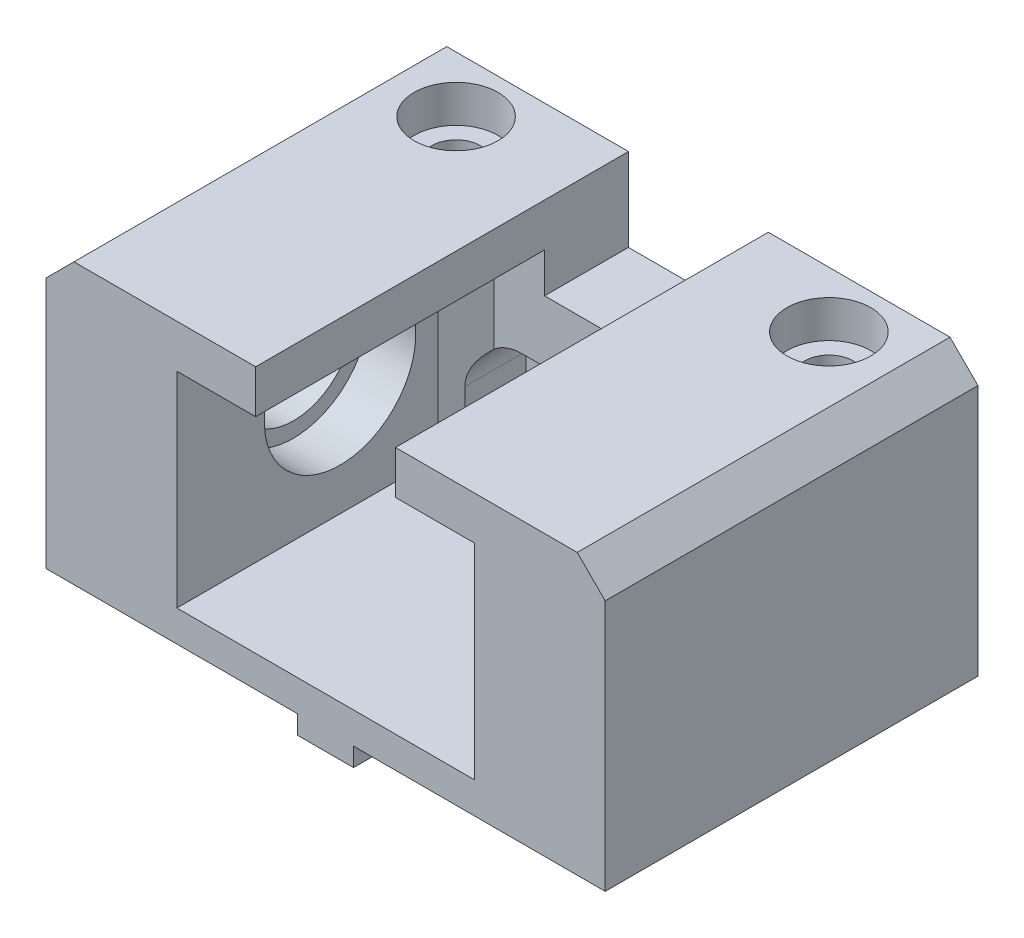
SolidWorks part; units mm, degrees
ref_plane "Front Plane" through (0, 0, 0) normal (0, 0, 1) x (1, 0, 0)
ref_plane "Top Plane" through (0, 0, 0) normal (0, 1, 0) x (1, 0, 0)
ref_plane "Right Plane" through (0, 0, 0) normal (1, 0, 0) x (0, 0, -1)
sketch "Sketch1" plane through (0, 0, 0) normal (0, 0, 1) x (1, 0, 0)
  line L0 (-7.5041, -0.2533) -> (-7.5041, -0.2824)
  line L1 (-5.65, -17.9827) -> (-5.65, -12.3454)
  line L2 (-5.65, -12.3454) -> (-5.15, -11.8454)
  line L3 (5.15, -11.8454) -> (5.65, -12.3454)
  line L4 (0, -17.9827) -> (0, 9.9476) construction
  line L5 (5.65, -17.9827) -> (5.65, -12.3454)
  line L6 (30, -21.3412) -> (30, 8.6588)
  line L7 (-15.9522, -17.9827) -> (15.9522, -17.9827)
  line L8 (-5.15, -11.8454) -> (5.15, -11.8454)
  line L27 (-30, -21.3412) -> (30, -21.3412)
  line L28 (-30, 8.6588) -> (-7.5, 8.6588)
  line L29 (7.5, 8.6588) -> (30, 8.6588)
  line L31 (15.9522, -17.9827) -> (15.9522, 4.0173)
  line L32 (-30, -21.3412) -> (-30, 8.6588)
  line L33 (-15.9522, 4.0173) -> (-7.5021, 4.0173)
  line L34 (7.5021, 4.0173) -> (15.9522, 4.0173)
  line L35 (-7.5, 8.6588) -> (-7.5021, 4.0173)
  line L36 (7.5, 8.6588) -> (7.5021, 4.0173)
  line L38 (-15.9522, -17.9827) -> (-15.9522, 4.0173)
  circle A2 centre (-10, -11.3412) radius 2.6
  circle A3 centre (10, -11.3412) radius 2.6
  point P3 (-5.65, -11.8454)
  point P7 (5.65, -11.8454)
  point P8 (-5.65, -11.3454)
  point P11 (5.65, -11.3454)
  dimension "D6" = 7.5
  dimension "D2" = 15
  dimension "D3" = 0.5
  dimension "D12" = 0.5
  dimension "D4" = 60
  dimension "D5" = 30
  dimension "D7" = 10
  dimension "D8" = 10
  dimension "D9" = 22
extrude "Boss-Extrude1" add sketch "Sketch1" along normal blind 40
sketch "Sketch2" plane through (0, 0, 0) normal (0, 0, -1) x (-1, 0, 0)
  line L0 (-7.5021, 4.0173) -> (-15.9522, 4.0173) construction
  line L1 (-15.9522, -17.9827) -> (-15.9522, 4.0173) construction
  line L3 (15.9522, -17.9827) -> (15.9522, 4.0173) construction
  line L4 (15.9522, 4.0173) -> (7.5021, 4.0173) construction
  line L5 (7.5, 8.6588) -> (7.5021, 4.0173) construction
  line L12 (5.5, -18.3454) -> (5.5244, -12.4844) construction
  line L13 (6.9689, -13.3454) -> (-4.795, -13.3457) construction
  line L14 (-7.5021, 8.6585) -> (-7.5021, -0.2536)
  line L15 (5.0208, -13.3455) -> (-5, -13.3457)
  line L16 (5.5188, -13.8455) -> (5.0208, -13.3455)
  line L17 (7.5041, -0.2533) -> (7.5041, -0.2824) construction
  line L19 (-7.5021, 4.0173) -> (-15.9522, 4.0173)
  line L20 (-15.9522, -17.9827) -> (-15.9522, 4.0173)
  line L22 (15.9522, -17.9827) -> (15.9522, 4.0173)
  line L23 (15.9522, 4.0173) -> (7.5021, 4.0173)
  line L24 (7.5, 8.6588) -> (7.5041, -0.2533)
  line L27 (30, -21.3454) -> (-28, -21.3454)
  line L31 (-5.5, -18.3457) -> (-5.5, -13.3436) construction
  line L32 (-5, -13.3457) -> (-5.5, -13.8457)
  line L33 (0, -18.3454) -> (0, -21.3454) construction
  line L36 (7.5041, -0.2533) -> (7.5041, -0.2824)
  line L37 (7.5041, -0.2533) -> (-7.5021, -0.2536)
  line L38 (5.5, -18.3454) -> (5.5188, -13.8455)
  line L42 (-5.5, -18.3457) -> (-5.5, -13.8457)
  line L54 (5.0298, -11.1846) -> (6.9689, -13.3454) construction
  line L55 (5, -18.3433) -> (5.0298, -11.1846) construction
  line L56 (5.8484, -12.8454) -> (-5.0021, -12.8457) construction
  line L57 (5.5244, -12.4844) -> (5.8484, -12.8454) construction
  line L58 (-5.0021, -12.8457) -> (-5.5, -13.3436) construction
  line L59 (-5, -18.3457) -> (-5, -13.5507) construction
  line L60 (-4.795, -13.3457) -> (-5, -13.5507) construction
  circle A0 centre (-10, -11.3412) radius 2.6 construction
  circle A1 centre (10, -11.3412) radius 2.6 construction
  circle A2 centre (-10, -11.3412) radius 2.6
  circle A3 centre (10, -11.3412) radius 2.6
  point P18 (5.5208, -13.3455)
  point P21 (-5.5, -13.3457)
  point P35 (5.65, -11.3454)
  point P38 (-5.15, -11.3454)
  point P40 (-5.65, -11.3454)
  point P42 (5.65, -11.3454)
  point P43 (-5.65, -11.3454)
  dimension "D2" = 5
  dimension "D3" = 11
  dimension "D1" = 0.5
  dimension "D11" = 0.5
  dimension "D4" = 5.5
extrude "Boss-Extrude2" add sketch "Sketch2" against normal blind 9
sketch "Sketch3" plane through (0, 0, 9) normal (0, 0, 1) x (1, 0, 0)
  circle A0 centre (-10, -11.3412) radius 4.5
  circle A1 centre (10, -11.3412) radius 4.5
  dimension "D1" = 9
extrude "Cut-Extrude1" cut sketch "Sketch3" against normal blind 5
sketch "Sketch4" plane through (0, 8.6588, 0) normal (0, 1, 0) x (1, 0, 0)
  line L0 (0, 0) -> (0, -35) construction
  circle A0 centre (-20, -6) radius 2.6
  circle A1 centre (20, -6) radius 2.6
  dimension "D1" = 5.2
  dimension "D2" = 6
  dimension "D3" = 20
extrude "Cut-Extrude2" cut sketch "Sketch4" against normal through all
chamfer "Chamfer1" distance 3 angle 45 2 edges at (-15.9522, -6.9827, 9) (15.9522, -6.9827, 9)
sketch "Sketch5" plane through (-30, 0, 0) normal (-1, 0, 0) x (0, 0, 1)
  circle A0 centre (22.5, -5.3412) radius 6.5
  dimension "D1" = 13
  dimension "D2" = 17.5
  dimension "D3" = 16
extrude "Cut-Extrude3" cut sketch "Sketch5" against normal blind 55
sketch "Sketch6" plane through (-30, 0, 0) normal (-1, 0, 0) x (0, 0, 1)
  circle A0 centre (22.5, -5.3412) radius 8.125
  dimension "D1" = 16.25
extrude "Cut-Extrude4" cut sketch "Sketch6" against normal blind 5
sketch "Sketch7" plane through (-15.9522, 0, 0) normal (1, 0, 0) x (0, 0, -1)
  circle A0 centre (-22.5, -5.3412) radius 8.125
  dimension "D1" = 16.25
extrude "Cut-Extrude5" cut sketch "Sketch7" against normal blind 5
sketch "Sketch8" plane through (15.9522, 0, 0) normal (-1, 0, 0) x (0, 0, 1)
  circle A0 centre (22.5, -5.3412) radius 8.125
  dimension "D1" = 16.25
extrude "Cut-Extrude6" cut sketch "Sketch8" against normal blind 5
sketch "Sketch9" plane through (0, 8.6588, 0) normal (0, 1, 0) x (1, 0, 0)
  circle A0 centre (20, -6) radius 4.5
  circle A1 centre (-20, -6) radius 4.5
  dimension "D1" = 9
extrude "Cut-Extrude7" cut sketch "Sketch9" against normal blind 4
chamfer "Chamfer2" distance 3 angle 45 2 edges at (-30, 8.6588, 20) (30, 8.6588, 20)
sketch "Sketch10" plane through (0, -21.3412, 0) normal (0, -1, 0) x (1, 0, 0)
  line L0 (0, 40) -> (0, 0) construction
  line L1 (-30, 40) -> (30, 40) construction
  line L2 (-30, 0) -> (30, 0) construction
  line L3 (-3, 40) -> (-3, 0)
  line L4 (3, 40) -> (3, 0)
  line L5 (3, 40) -> (-3, 40)
  line L6 (3, 0) -> (-3, 0)
  dimension "D1" = 3
extrude "Boss-Extrude3" add sketch "Sketch10" along normal blind 2
sketch "Sketch11" plane through (0, 0, 9) normal (0, 0, 1) x (1, 0, 0)
  line L0 (-10, -6.8412) -> (10, -6.8412)
  line L1 (-14.5, -11.3412) -> (-14.4522, -17.9827)
  line L2 (-12.9522, -17.9827) -> (-15.9522, -17.9827) construction
  line L3 (14.5, -11.3412) -> (14.4522, -17.9827)
  line L4 (15.9522, -17.9827) -> (12.9522, -17.9827) construction
  line L5 (14.4522, -17.9827) -> (-14.4522, -17.9827)
  circle A0 centre (-10, -11.3412) radius 4.5 construction
  arc A1 (-12.9522, -14.7375) -> (-12.9522, -7.945) centre (-10, -11.3412) ccw construction
  circle A2 centre (10, -11.3412) radius 4.5 construction
  arc A3 (12.9522, -7.945) -> (12.9522, -14.7375) centre (10, -11.3412) ccw construction
  arc A4 (-12.9522, -7.945) -> (-12.9522, -14.7375) centre (-10, -11.3412) ccw construction
  arc A5 (12.9522, -14.7375) -> (12.9522, -7.945) centre (10, -11.3412) ccw construction
  arc A6 (-14.5, -11.3412) -> (-14.4995, -11.406) centre (-10, -11.3412) ccw
  arc A7 (14.4995, -11.406) -> (14.5, -11.3412) centre (10, -11.3412) ccw
  arc A8 (-14.5, -11.3412) -> (-10, -6.8412) centre (-10, -11.3412) ccw
  arc A9 (10, -6.8412) -> (14.5, -11.3412) centre (10, -11.3412) ccw
  arc M3 (-12.9522, -7.945) -> (-12.9522, -14.7375) centre (-10, -11.3412) cw
  line M4 (-12.9522, -14.7375) -> (-12.9522, -17.9827)
  line M5 (-12.9522, -17.9827) -> (-5.5015, -17.9827)
  line M6 (-5.5015, -17.9827) -> (-5.5188, -13.8455)
  line M7 (-5.5188, -13.8455) -> (-5.0208, -13.3455)
  line M8 (-5.0208, -13.3455) -> (5, -13.3457)
  line M9 (5, -13.3457) -> (5.5, -13.8457)
  line M10 (5.5, -13.8457) -> (5.5, -17.9827)
  line M11 (5.5, -17.9827) -> (12.9522, -17.9827)
  line M12 (12.9522, -17.9827) -> (12.9522, -14.7375)
  arc M13 (12.9522, -14.7375) -> (12.9522, -7.945) centre (10, -11.3412) cw
extrude "Cut-Extrude8" cut sketch "Sketch11" against normal up to surface (5 mm away) contours L0 M3 M4 M5 M6 M7 M8 M9 M10 M11 M12 M13 | A8 L1 L5 M4 | A9 L5 L3 M12 up to face at (-5.5, -11.3412, 4)
sketch "Sketch13" plane through (0, 0, 40) normal (0, 0, 1) x (1, 0, 0)
  line L0 (-14.5, -11.3412) -> (-14.4522, -17.9827)
  line L1 (-12.9522, -17.9827) -> (-15.9522, -17.9827) construction
  line L2 (-14.4522, -17.9827) -> (14.4522, -17.9827)
  line L3 (15.9522, -17.9827) -> (12.9522, -17.9827) construction
  line L4 (14.4522, -17.9827) -> (14.5, -11.3412)
  line L5 (14.5, -11.3412) -> (-14.5, -11.3412)
  arc A0 (-12.9522, -7.945) -> (-12.9522, -14.7375) centre (-10, -11.3412) ccw construction
  arc A1 (12.9522, -14.7375) -> (12.9522, -7.945) centre (10, -11.3412) ccw construction
extrude "Cut-Extrude9" cut sketch "Sketch13" against normal up to surface (36 mm away) up to face at (-0.0034, -13.4104, 4)
